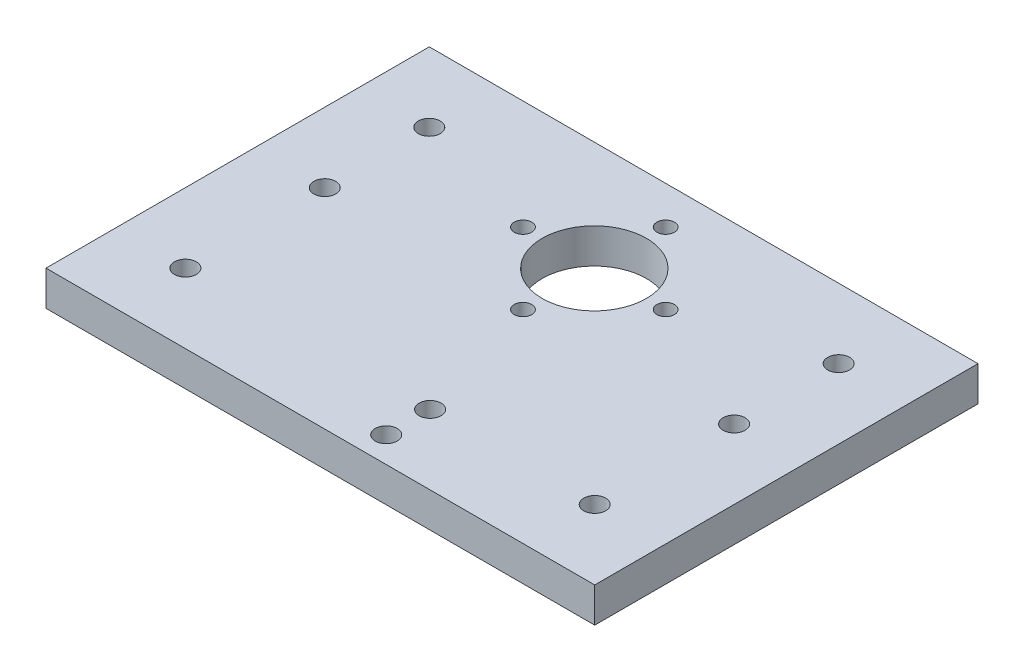
SolidWorks part; units mm, degrees
ref_plane "Front Plane" through (0, 0, 0) normal (0, 0, 1) x (1, 0, 0)
ref_plane "Top Plane" through (0, 0, 0) normal (0, 1, 0) x (1, 0, 0)
ref_plane "Right Plane" through (0, 0, 0) normal (1, 0, 0) x (0, 0, -1)
sketch "Sketch1" plane through (0, 0, 0) normal (0, 1, 0) x (1, 0, 0)
  line L0 (-37.3, 3.175) -> (37.3, 3.175) construction
  line L1 (-50, 34.925) -> (50, 34.925)
  line L2 (-50, 34.925) -> (-50, -34.925)
  line L3 (-50, -34.925) -> (50, -34.925)
  line L4 (50, 34.925) -> (50, -34.925)
  line L5 (-50, 34.925) -> (50, -34.925) construction
  line L6 (-50, -34.925) -> (50, 34.925) construction
  line L7 (24.6, -34.925) -> (50, -34.925) construction
  line L8 (7.3, -30.225) -> (7.3, -22.225) construction
  line L9 (-37.3, -22.225) -> (37.3, -22.225) construction
  line L10 (-37.3, -22.225) -> (-37.3, 22.225) construction
  line L11 (-37.3, 22.225) -> (37.3, 22.225) construction
  line L12 (37.3, -22.225) -> (37.3, 22.225) construction
  line L13 (-37.3, -22.225) -> (37.3, 22.225) construction
  line L14 (-37.3, 22.225) -> (37.3, -22.225) construction
  line L15 (0, 0) -> (0, 15) construction
  line L16 (7.3, -30.225) -> (20.8, -30.225) construction
  line L17 (24.6, -34.925) -> (24.6, -9.525) construction
  line L18 (24.6, -9.525) -> (50, -9.525) construction
  line L19 (50, -34.925) -> (50, -9.525) construction
  line L20 (24.6, -34.925) -> (50, -9.525) construction
  line L21 (24.6, -9.525) -> (50, -34.925) construction
  circle A18 centre (-37.3, 22.225) radius 2
  circle A19 centre (37.3, 22.225) radius 2
  circle A20 centre (37.3, -22.225) radius 2
  circle A21 centre (-37.3, -22.225) radius 2
  circle A22 centre (7.3, -30.225) radius 2
  circle A23 centre (7.3, -22.225) radius 2
  circle A24 centre (0, 15) radius 9.5
  circle A25 centre (0, 15) radius 13 construction
  circle A26 centre (0, 28) radius 1.5 construction
  circle A27 centre (-13, 15) radius 1.5 construction
  circle A28 centre (13, 15) radius 1.5 construction
  circle A29 centre (0, 2) radius 1.5 construction
  circle A30 centre (-37.3, 3.175) radius 2
  circle A31 centre (37.3, 3.175) radius 2
  dimension "D2" = 30
  dimension "D4" = 19
  dimension "D7" = 26
  dimension "D10" = 4
  dimension "D13" = 12.7
  dimension "D15" = 4
  dimension "D16" = 8
  dimension "D17" = 4
  dimension "D9" = 3
  dimension "D5" = 15
  dimension "D6" = 100
  dimension "D8" = 69.85
  dimension "D11" = 25.4
  dimension "D14" = 12.7
  dimension "D3" = 13.5
extrude "Boss-Extrude1" add sketch "Sketch1" along normal blind 6.35
hole_wizard "CSK for M3 Flat Head Machine Screw1" positions "Sketch7" profile "Sketch8" countersink size "M3" standard "ANSI Metric" end condition through all
sketch "Sketch7" plane through (0, 0, 0) normal (0, -1, 0) x (-1, 0, 0)
  point P0 (-13, 15)
  point P3 (0, 2)
  point P6 (13, 15)
  point P9 (0, 28)
sketch "Sketch8" plane through (13, 0, -15) normal (1, 0, 0) x (0, 0, -1)
  line L0 (0, 0) -> (0, 6.35)
  line L1 (0, 6.35) -> (1.6, 6.35)
  line L2 (1.6, 6.35) -> (1.6, 1.55)
  line L3 (1.6, 1.55) -> (3.15, 0)
  line L5 (3.15, 0) -> (0, 0)
  line L6 (-1.6, 1.55) -> (-3.15, 0) construction
  line L11 (0, -6.35) -> (0, 107.95) construction
  dimension "Thru Hole Dia." = 3.2
  dimension "Thru Hole Depth" = 6.35
  dimension "Near C'Sink Dia." = 6.3
  dimension "Near C'Sink Angle" = 90
equation "\"testbed_height\" = 91.50mm"
equation "\"plate_thickness\" = 6mm"
equation "\"main_body_splay_length\" = 48.5mm"
equation "\"splay_shaft_length_no_wires\" = 10mm"
equation "\"splay_shaft_length_wires\" = 6.5mm"
equation "\"timing_pulley_offset\" = 0mm"
equation "\"effective_motor_length\" = \"timing_pulley_offset\" + \"splay_shaft_length_no_wires\" + \"main_body_splay_length\""
equation "\"80_20_side\" = 25.4mm"
equation "\"80_20_length\" = 152.4mm"
equation "\"80_20_optic_mount_length\" = \"80_20_length\" - 25.4mm"
equation "\"optic_board_hole_size\" = 6.35mm"
equation "\"total_mounting_length\" = \"testbed_height\" - \"effective_motor_length\" - \"80_20_side\""
equation "\"mounting_vertical_portion_height\" = \"total_mounting_length\" - 2 * \"plate_thickness\""
equation "\"face_mount_width\" = 15.25mm"
equation "\"center_dist_to_face_mount_vertical_screws\" = 5mm"
equation "\"D1@Boss-Extrude1\"=0.25in"
